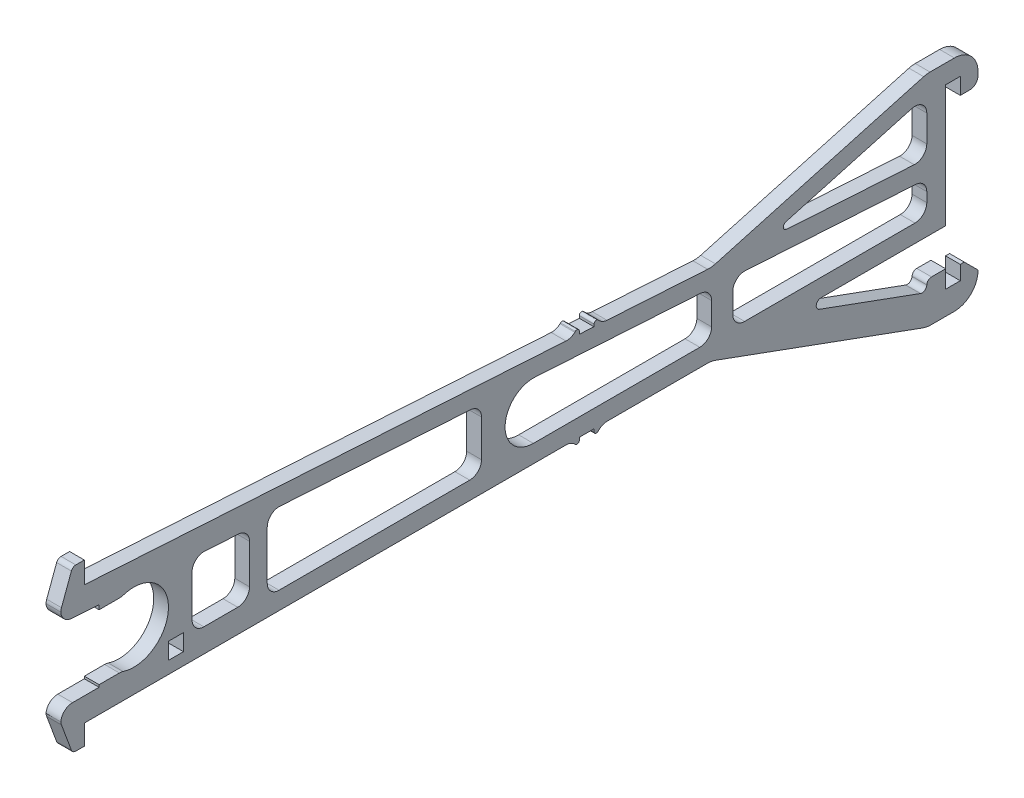
SolidWorks part; units mm, degrees
material "Delrin"
ref_plane "Front Plane" through (0, 0, 0) normal (0, 0, 1) x (1, 0, 0)
ref_plane "Top Plane" through (0, 0, 0) normal (0, 1, 0) x (1, 0, 0)
ref_plane "Right Plane" through (0, 0, 0) normal (1, 0, 0) x (0, 0, -1)
sketch "Sketch1" plane through (0, 0, 0) normal (1, 0, 0) x (0, 0, -1)
  line L0 (0.3859, 6.2619) -> (62.1851, 2.453)
  line L1 (0, -6.2738) -> (62.1851, -6.2738)
  line L2 (85.344, 8.8996) -> (88.3158, 8.8996)
  line L3 (12.4587, 2.973) -> (0.2297, 3.7267)
  line L4 (12.4587, -3.7338) -> (0, -3.7338)
  line L5 (-5.3213, -3.7338) -> (-7.8613, -3.7338)
  line L6 (45.3857, 3.4884) -> (45.3857, 1.5834) construction
  line L7 (85.344, -6.2738) -> (85.344, 8.8996) construction
  line L8 (-5.3213, -0.4002) -> (-5.3213, 21.638) construction
  line L9 (0.3859, 6.2619) -> (-5.3213, 6.6137)
  line L10 (-5.3213, 6.6137) -> (-5.3213, 8.9244)
  line L11 (-5.3213, 8.9244) -> (-7.8613, 8.9244)
  line L12 (-7.8613, 8.9244) -> (-7.8613, 4.2254)
  line L13 (14.3637, 3.4954) -> (14.3637, 5.4004) construction
  line L14 (0, -6.2738) -> (-5.3213, -6.2738)
  line L15 (-5.3213, -6.2738) -> (-5.3213, -8.4328)
  line L16 (14.3637, 3.4954) -> (14.3637, -4.3688)
  line L17 (39.3251, 1.9569) -> (39.3251, -4.3688)
  line L18 (37.4201, 2.0744) -> (37.4201, -4.3688)
  line L19 (-5.3213, -8.4328) -> (-7.8613, -8.4328)
  line L20 (-7.8613, -8.4328) -> (-7.8613, -3.7338)
  line L21 (45.3857, -4.3688) -> (45.3857, -6.2738) construction
  line L22 (12.4587, 2.973) -> (12.4587, -3.7338)
  line L23 (0, 3.7338) -> (0, -3.7338)
  line L24 (89.9668, 5.0896) -> (88.9508, 5.0896)
  line L25 (88.9508, 5.0896) -> (88.9508, 6.8676)
  line L26 (88.9508, 6.8676) -> (87.376, 6.8676)
  line L27 (87.376, 6.8676) -> (87.376, -6.2738)
  line L28 (87.376, -12.1824) -> (88.9508, -12.1824)
  line L29 (88.9508, -12.1824) -> (88.9508, -10.6584)
  line L30 (88.9508, -10.6584) -> (89.3826, -10.6584)
  line L31 (90.8558, -12.1316) -> (90.8558, -12.1824)
  line L32 (88.3158, -14.7224) -> (85.344, -14.7224)
  line L33 (85.344, -14.7224) -> (85.344, -6.2738) construction
  line L34 (90.8558, 5.9786) -> (90.8558, 6.3596)
  line L35 (89.3826, -10.6584) -> (90.8558, -12.1316)
  line L36 (64.4711, 0.4071) -> (64.4711, -4.3688)
  line L37 (62.1851, 0.548) -> (62.1851, -4.3688)
  line L38 (62.1851, 2.453) -> (85.344, 8.8996)
  line L39 (68.0011, 2.0945) -> (85.344, 6.9222)
  line L40 (62.1851, -6.2738) -> (85.344, -14.7224)
  line L41 (71.0788, -6.2738) -> (85.344, -11.4779)
  line L42 (63.2297, -3.4104) -> (86.3886, -11.859) construction
  line L43 (62.696, 0.6178) -> (85.8549, 7.0644) construction
  line L44 (71.0788, -6.2738) -> (85.344, -6.2738)
  line L45 (-1.3313, 3.4884) -> (-3.7338, 3.4884)
  line L46 (68.0011, 2.0945) -> (85.344, 1.0256)
  line L47 (62.1851, -4.3688) -> (62.1851, 49995.6312) construction
  line L48 (85.344, 6.9222) -> (85.344, 1.0256)
  line L49 (85.344, -0.8794) -> (85.344, -4.3688)
  line L50 (87.376, -12.1824) -> (87.376, -10.2774)
  line L51 (85.344, -6.2738) -> (87.376, -6.2738)
  line L52 (87.376, -10.2774) -> (85.344, -10.2774)
  line L53 (85.344, -10.2774) -> (85.344, -11.4779)
  line L54 (14.3637, 3.4954) -> (37.4201, 2.0744)
  line L55 (14.3637, -4.3688) -> (37.4201, -4.3688)
  line L56 (39.3251, -4.3688) -> (62.1851, -4.3688)
  line L57 (39.3251, 1.9569) -> (62.1851, 0.548)
  line L58 (64.4711, 0.4071) -> (85.344, -0.8794)
  line L59 (64.4711, -4.3688) -> (85.344, -4.3688)
  line L60 (-3.7338, 0) -> (-3.7338, 17.9839) construction
  line L61 (-3.7338, 3.971) -> (-7.8613, 4.2254)
  line L62 (-3.7338, -3.7338) -> (-5.3213, -3.7338)
  line L63 (-3.7338, 3.4884) -> (-3.7338, 3.971)
  line L64 (-1.3313, -3.4884) -> (-3.7338, -3.4884)
  line L65 (-3.7338, -3.4884) -> (-3.7338, -3.7338)
  line L66 (6.2738, 3.3542) -> (6.2738, -3.7338)
  line L67 (3.7338, 0) -> (3.7338, 11.926) construction
  arc A0 (0, -3.7338) -> (0, 3.7338) centre (0, 0) ccw
  circle A1 centre (0, 0) radius 6.2738 construction
  arc A2 (88.3158, 8.8996) -> (90.8558, 6.3596) centre (88.3158, 6.3596) cw
  arc A3 (90.8558, -12.1824) -> (88.3158, -14.7224) centre (88.3158, -12.1824) cw
  arc A4 (90.8558, 5.9786) -> (89.9668, 5.0896) centre (89.9668, 5.9786) cw
  arc A5 (0, 3.7338) -> (-1.3313, 3.4884) centre (0, 0) ccw
  circle A6 centre (0, 0) radius 3.7338 construction
  arc A7 (-1.3313, -3.4884) -> (0, -3.7338) centre (0, 0) ccw
  point P47 (90.8558, 8.8996)
  point P50 (90.8558, -14.7224)
  point P53 (90.8558, 5.0896)
  point P54 (90.8558, -10.6584)
  point P56 (90.8558, -10.6584)
  point P79 (3.5707, 1.0917)
  dimension "D1" = 7.4676
  dimension "D2" = 2.54
  dimension "D3" = 5.842
  dimension "D8" = 1.5748
  dimension "D18" = 2.54
  dimension "D19" = 2.54
  dimension "D20" = 0.889
  dimension "D21" = 22.86
  dimension "D5" = 37.4201
  dimension "D10" = 1.905
  dimension "D11" = 1.778
  dimension "D12" = 1.905
  dimension "D4" = 5.3842
  dimension "D9" = 1.5748
  dimension "D14" = 1.524
  dimension "D15" = 3.81
  dimension "D16" = 4.064
  dimension "D17" = 1.905
  dimension "D22" = 19.05
  dimension "D23" = 85.344
  dimension "D24" = 2.032
  dimension "D25" = 2.286
  dimension "D29" = 1.905
  dimension "D13" = 2.54
  dimension "D30" = 4.699
  dimension "D31" = 1.905
  dimension "D32" = 17.78
  dimension "D33" = 1.5875
  dimension "D6" = 1.905
  dimension "D7" = 0.4826
  dimension "D34" = 2.54
  dimension "D27" = 3.048
  dimension "D28" = 1.905
extrude "Boss-Extrude1" add sketch "Sketch1" along normal blind 1.5875 contours A1 A0 | A4 L34 A2 L2 L38 L0 L9 L10 L11 L12 L49 L20 L19 L15 L14 L1 L40 L32 A3 L31 L35 L30 L29 L28 L50 L52 L53 L41 L44 L51 L27 L26 L25 L24 | L18 L17 | L22 L16 | L37 L36 region at (0, 3.3443, -31.2231) region at (0, -0.1773, -4.5129)
sketch "Sketch7" plane through (0, 0, 0) normal (-1, 0, 0) x (0, 0, 1)
  line L0 (6.5913, 8.9244) -> (7.8613, 5.4954)
  line L1 (5.3213, 8.9244) -> (7.8613, 8.9244) construction
  line L2 (7.8613, 8.9244) -> (7.8613, 4.2254) construction
  line L3 (6.5913, 8.9244) -> (7.8613, 8.9244)
  line L4 (7.8613, 8.9244) -> (7.8613, 5.4954)
  line L5 (6.5913, -8.4328) -> (7.8613, -5.0038)
  line L6 (5.3213, -8.4328) -> (7.8613, -8.4328) construction
  line L7 (7.8613, -8.4328) -> (7.8613, -3.7338) construction
  line L8 (6.5913, -8.4328) -> (7.8613, -8.4328)
  line L9 (7.8613, -8.4328) -> (7.8613, -5.0038)
  dimension "D1" = 1.27
  dimension "D2" = 1.27
  dimension "D3" = 1.27
extrude "Cut-Extrude2" cut sketch "Sketch7" against normal through all
fillet "Fillet1" radius 2.54 4 edges at (0.7937, 2.453, -62.1851) (0.7937, 8.8996, -85.344) (0.7937, -6.2738, -62.1851) (0.7937, -14.7224, -85.344)
fillet "Fillet2" radius 1.27 16 edges at (0.7937, 1.0256, -85.344) (0.7937, 6.9222, -85.344) (0.7937, -4.3688, -14.3637) (0.7937, 3.4954, -14.3637) (0.7937, 2.0744, -37.4201) (0.7937, -4.3688, -37.4201) (0.7937, -4.3688, -64.4711) (0.7937, 0.4071, -64.4711) (0.7937, -4.3688, -85.344) (0.7937, -0.8794, -85.344) (0.7937, -4.3688, -62.1851) (0.7937, 0.548, -62.1851) (0.7937, -3.7338, -6.2738) (0.7937, 3.3542, -6.2738) (0.7937, -3.7338, -12.4587) (0.7937, 2.973, -12.4587)
fillet "Fillet3" radius 0.508 2 edges at (0.7937, -6.2738, -71.0788) (0.7937, -11.4779, -85.344)
fillet "Fillet4" radius 0.508 1 edges at (0.7937, -10.2774, -85.344)
sketch "Sketch4" plane through (1.5875, 0, 0) normal (1, 0, 0) x (0, 0, -1)
  line L0 (39.3251, 1.9569) -> (60.9932, 0.6215) construction
  line L1 (39.3251, -4.3688) -> (60.9151, -4.3688) construction
  line L2 (39.9601, -1.3223) -> (39.3251, -1.3223) construction
  line L6 (39.3251, 1.9569) -> (39.3251, -4.3688) construction
  line L7 (39.3251, 1.9569) -> (43.194, 1.7185)
  line L8 (39.3251, 1.9569) -> (39.3251, -4.3688)
  line L9 (39.3251, -4.3688) -> (43.0066, -4.3688)
  arc A0 (43.194, 1.7185) -> (43.0066, -4.3688) centre (43.0066, -1.3223) ccw
  dimension "D1" = 0.635
sketch "Sketch6" plane through (1.5875, 0, 0) normal (-1, 0, 0) x (0, 0, 1)
  line L0 (-47.0577, -6.2738) -> (-47.9467, -7.1628)
  line L1 (5.3213, 6.6137) -> (-61.759, 2.4793) construction
  line L2 (-47.9467, -17.1193) -> (-47.9467, 10.2613) construction
  line L3 (-47.9467, -7.1628) -> (-47.9467, -6.2738)
  line L4 (-47.9467, -6.2738) -> (-47.0577, -6.2738)
  line L5 (-61.7363, -6.2738) -> (5.3213, -6.2738) construction
  line L6 (-48.7404, -10.0838) -> (-48.7404, 6.4573) construction
  line L7 (-49.5342, -10.0838) -> (-47.9467, -10.0838) construction
  line L8 (-49.5342, -6.2738) -> (-50.4232, -6.2738)
  line L9 (-49.5342, -7.1628) -> (-49.5342, -6.2738)
  line L10 (-50.4232, -6.2738) -> (-49.5342, -7.1628)
  line L11 (-50.4215, 3.178) -> (-49.5342, 4.1217)
  line L13 (-49.5342, -17.1193) -> (-49.5342, 10.2613) construction
  line L14 (-49.5342, 4.1217) -> (-49.5342, 3.2327)
  line L15 (-49.5342, 3.2327) -> (-50.4215, 3.178)
  line L16 (-47.9467, 3.3306) -> (-47.0594, 3.3853)
  line L17 (-47.0594, 3.3853) -> (-47.9467, 4.2196)
  line L18 (-47.9467, 4.2196) -> (-47.9467, 3.3306)
  dimension "D1" = 0.889
extrude "Boss-Extrude3" add sketch "Sketch6" along normal up to surface (1.5875 mm away) contours L4 L3 L0 | L8 L10 L9 | L15 L14 L11 | L17 L18 L16 | L18 L17 L16 | L14 L15 L11 | L10 L8 L9 | L3 L4 L0 region at (1.5875, -6.5701, -47.6504) region at (1.5875, -6.5701, -49.8305) region at (1.5875, 3.5108, -49.83) region at (1.5875, 3.6451, -47.6509) up to face at (0, -2.6403, -52.018)
fillet "Fillet5" radius 1.27 4 edges at (0.7937, 3.178, -50.4215) (0.7937, 3.3853, -47.0594) (0.7937, -6.2738, -50.4232) (0.7937, -6.2738, -47.0577)
fillet "Fillet6" radius 0.254 4 edges at (0.7937, -7.1628, -49.5342) (0.7937, -7.1628, -47.9467) (0.7937, 4.2196, -47.9467) (0.7937, 4.1217, -49.5342)
extrude "Boss-Extrude4" add sketch "Sketch4" against normal up to surface (1.5875 mm away) up to face at (0, -2.2883, -51.0099)
sketch "Sketch5" plane through (1.5875, 0, 0) normal (1, 0, 0) x (0, 0, -1)
  line L8 (3.7592, -4.445) -> (3.7592, -4.953) construction
  line L9 (3.7592, -4.953) -> (5.3467, -4.953) construction
  line L10 (5.3467, -4.953) -> (5.3467, -4.445) construction
  line L11 (5.3467, -4.445) -> (5.3467, -3.683) construction
  line L12 (5.3467, -3.683) -> (5.3467, -3.175) construction
  line L13 (5.3467, -3.175) -> (3.7592, -3.175) construction
  line L14 (3.7592, -3.175) -> (3.7592, -3.683) construction
  line L15 (3.7592, -4.445) -> (3.7592, -3.683) construction
  line L16 (3.7592, -4.445) -> (3.7592, -4.953)
  line L17 (3.7592, -4.953) -> (5.3467, -4.953)
  line L18 (5.3467, -4.953) -> (5.3467, -4.445)
  line L19 (5.3467, -4.445) -> (5.3467, -3.683)
  line L20 (5.3467, -3.683) -> (5.3467, -3.175)
  line L21 (5.3467, -3.175) -> (3.7592, -3.175)
  line L22 (3.7592, -3.175) -> (3.7592, -3.683)
  line L23 (3.7592, -4.445) -> (3.7592, -3.683)
extrude "Cut-Extrude1" cut sketch "Sketch5" against normal up to next
fillet "Fillet9" radius 1.27 2 edges at (0.7937, -3.4884, 1.3313) (0.7937, 3.4884, 1.3313)
fillet "Fillet10" radius 0.381 1 edges at (0.7937, 2.0945, -68.0011)
fillet "Fillet12" radius 1.27 4 edges at (0.7937, -5.0038, 7.8613) (0.7937, -3.7338, 7.8613) (0.7937, 5.4954, 7.8613) (0.7937, 4.2254, 7.8613)
fillet "Fillet13" radius 0.508 2 edges at (0.7937, 8.9244, 6.5913) (0.7937, -8.4328, 6.5913)
